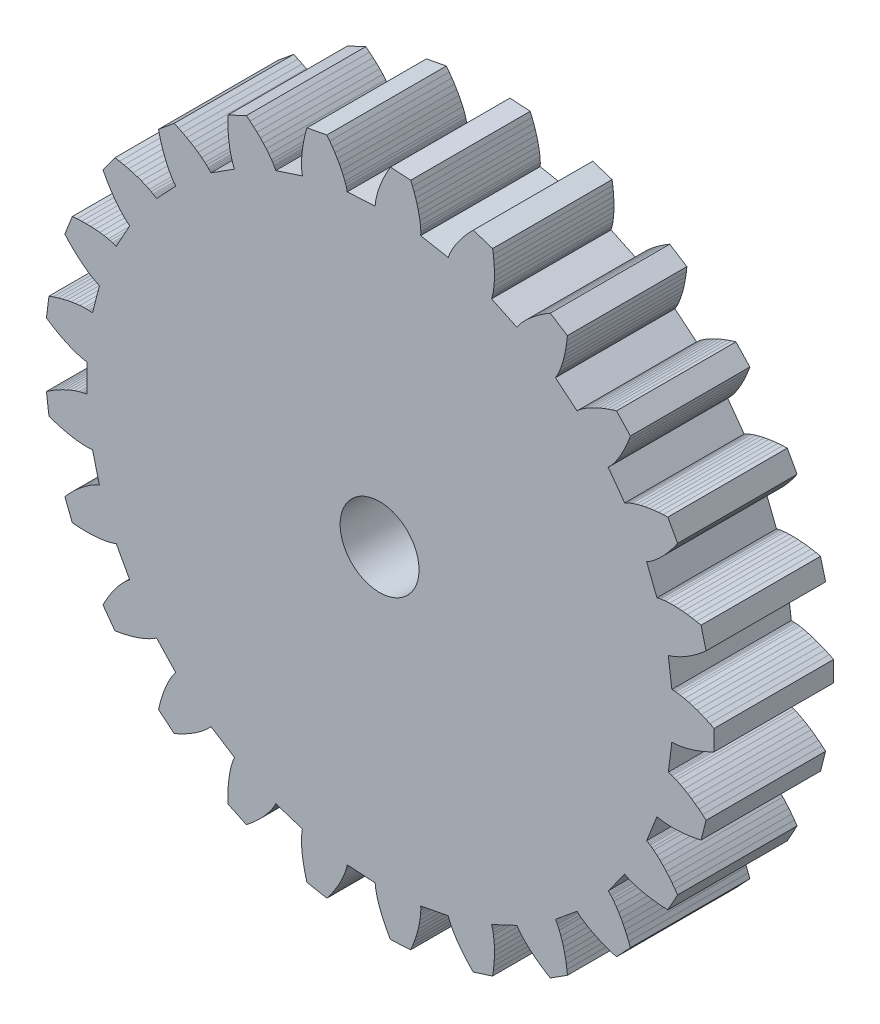
SolidWorks part; units mm, degrees
ref_plane "Front Plane" through (0, 0, 0) normal (0, 0, 1) x (1, 0, 0)
ref_plane "Top Plane" through (0, 0, 0) normal (0, 1, 0) x (1, 0, 0)
ref_plane "Right Plane" through (0, 0, 0) normal (1, 0, 0) x (0, 0, -1)
sketch "Model" plane through (0, 0, 0) normal (0, 0, 1) x (1, 0, 0)
  line L0 (22.5153, 13.4937) -> (22.5501, 13.4944)
  line L1 (22.5501, 13.4944) -> (22.5851, 13.4936)
  line L2 (22.5851, 13.4936) -> (22.6201, 13.4916)
  line L3 (22.6201, 13.4916) -> (22.6552, 13.4888)
  line L4 (22.6552, 13.4888) -> (22.7255, 13.481)
  line L5 (22.7255, 13.481) -> (22.796, 13.4706)
  line L6 (22.796, 13.4706) -> (22.9373, 13.4433)
  line L7 (22.9373, 13.4433) -> (23.079, 13.4085)
  line L8 (23.079, 13.4085) -> (23.221, 13.3669)
  line L9 (23.221, 13.3669) -> (23.363, 13.3191)
  line L10 (23.363, 13.3191) -> (23.5051, 13.2655)
  line L11 (23.5051, 13.2655) -> (23.647, 13.2062)
  line L12 (23.647, 13.2062) -> (23.7888, 13.1416)
  line L13 (23.7888, 13.1416) -> (23.9303, 13.0718)
  line L14 (23.9303, 13.0718) -> (23.9303, 12.3915)
  line L15 (23.9303, 12.3915) -> (23.7888, 12.3217)
  line L16 (23.7888, 12.3217) -> (23.647, 12.257)
  line L17 (23.647, 12.257) -> (23.5051, 12.1978)
  line L18 (23.5051, 12.1978) -> (23.363, 12.1441)
  line L19 (23.363, 12.1441) -> (23.221, 12.0963)
  line L20 (23.221, 12.0963) -> (23.079, 12.0548)
  line L21 (23.079, 12.0548) -> (22.9373, 12.0199)
  line L22 (22.9373, 12.0199) -> (22.796, 11.9927)
  line L23 (22.796, 11.9927) -> (22.7255, 11.9823)
  line L24 (22.7255, 11.9823) -> (22.6552, 11.9745)
  line L25 (22.6552, 11.9745) -> (22.6201, 11.9716)
  line L26 (22.6201, 11.9716) -> (22.5851, 11.9697)
  line L27 (22.5851, 11.9697) -> (22.5501, 11.9688)
  line L28 (22.5501, 11.9688) -> (22.5153, 11.9696)
  line L29 (22.5153, 11.9696) -> (22.3975, 11.0367)
  line L30 (22.3975, 11.0367) -> (22.4314, 11.0287)
  line L31 (22.4314, 11.0287) -> (22.465, 11.0192)
  line L32 (22.465, 11.0192) -> (22.4984, 11.0086)
  line L33 (22.4984, 11.0086) -> (22.5317, 10.9971)
  line L34 (22.5317, 10.9971) -> (22.5978, 10.9721)
  line L35 (22.5978, 10.9721) -> (22.6635, 10.9445)
  line L36 (22.6635, 10.9445) -> (22.7937, 10.8829)
  line L37 (22.7937, 10.8829) -> (22.9223, 10.8139)
  line L38 (22.9223, 10.8139) -> (23.0494, 10.7384)
  line L39 (23.0494, 10.7384) -> (23.1751, 10.6567)
  line L40 (23.1751, 10.6567) -> (23.2994, 10.5694)
  line L41 (23.2994, 10.5694) -> (23.4221, 10.4767)
  line L42 (23.4221, 10.4767) -> (23.5434, 10.3789)
  line L43 (23.5434, 10.3789) -> (23.6631, 10.2761)
  line L44 (23.6631, 10.2761) -> (23.4939, 9.6172)
  line L45 (23.4939, 9.6172) -> (23.3395, 9.5847)
  line L46 (23.3395, 9.5847) -> (23.1861, 9.5574)
  line L47 (23.1861, 9.5574) -> (23.0339, 9.5353)
  line L48 (23.0339, 9.5353) -> (22.8829, 9.5187)
  line L49 (22.8829, 9.5187) -> (22.7334, 9.5077)
  line L50 (22.7334, 9.5077) -> (22.5856, 9.5027)
  line L51 (22.5856, 9.5027) -> (22.4397, 9.5042)
  line L52 (22.4397, 9.5042) -> (22.296, 9.513)
  line L53 (22.296, 9.513) -> (22.2251, 9.5205)
  line L54 (22.2251, 9.5205) -> (22.1551, 9.5304)
  line L55 (22.1551, 9.5304) -> (22.1204, 9.5364)
  line L56 (22.1204, 9.5364) -> (22.086, 9.5432)
  line L57 (22.086, 9.5432) -> (22.0519, 9.551)
  line L58 (22.0519, 9.551) -> (22.0184, 9.5604)
  line L59 (22.0184, 9.5604) -> (21.6723, 8.6861)
  line L60 (21.6723, 8.6861) -> (21.7031, 8.67)
  line L61 (21.7031, 8.67) -> (21.7333, 8.6524)
  line L62 (21.7333, 8.6524) -> (21.7631, 8.6338)
  line L63 (21.7631, 8.6338) -> (21.7925, 8.6145)
  line L64 (21.7925, 8.6145) -> (21.8503, 8.5737)
  line L65 (21.8503, 8.5737) -> (21.9071, 8.5306)
  line L66 (21.9071, 8.5306) -> (22.0178, 8.4387)
  line L67 (22.0178, 8.4387) -> (22.1252, 8.3399)
  line L68 (22.1252, 8.3399) -> (22.2296, 8.2351)
  line L69 (22.2296, 8.2351) -> (22.331, 8.1247)
  line L70 (22.331, 8.1247) -> (22.4297, 8.0093)
  line L71 (22.4297, 8.0093) -> (22.5255, 7.889)
  line L72 (22.5255, 7.889) -> (22.6186, 7.764)
  line L73 (22.6186, 7.764) -> (22.709, 7.6347)
  line L74 (22.709, 7.6347) -> (22.3812, 7.0385)
  line L75 (22.3812, 7.0385) -> (22.2236, 7.0455)
  line L76 (22.2236, 7.0455) -> (22.0683, 7.0572)
  line L77 (22.0683, 7.0572) -> (21.9153, 7.0737)
  line L78 (21.9153, 7.0737) -> (21.765, 7.0951)
  line L79 (21.765, 7.0951) -> (21.6175, 7.1216)
  line L80 (21.6175, 7.1216) -> (21.473, 7.1536)
  line L81 (21.473, 7.1536) -> (21.3321, 7.1913)
  line L82 (21.3321, 7.1913) -> (21.1951, 7.2356)
  line L83 (21.1951, 7.2356) -> (21.1283, 7.2604)
  line L84 (21.1283, 7.2604) -> (21.0629, 7.2874)
  line L85 (21.0629, 7.2874) -> (21.0308, 7.3018)
  line L86 (21.0308, 7.3018) -> (20.9992, 7.317)
  line L87 (20.9992, 7.317) -> (20.9681, 7.3331)
  line L88 (20.9681, 7.3331) -> (20.938, 7.3505)
  line L89 (20.938, 7.3505) -> (20.3853, 6.5898)
  line L90 (20.3853, 6.5898) -> (20.4112, 6.5665)
  line L91 (20.4112, 6.5665) -> (20.4361, 6.5419)
  line L92 (20.4361, 6.5419) -> (20.4602, 6.5165)
  line L93 (20.4602, 6.5165) -> (20.4839, 6.4905)
  line L94 (20.4839, 6.4905) -> (20.5298, 6.4366)
  line L95 (20.5298, 6.4366) -> (20.574, 6.3808)
  line L96 (20.574, 6.3808) -> (20.6584, 6.2642)
  line L97 (20.6584, 6.2642) -> (20.7379, 6.1418)
  line L98 (20.7379, 6.1418) -> (20.8129, 6.0143)
  line L99 (20.8129, 6.0143) -> (20.8838, 5.8822)
  line L100 (20.8838, 5.8822) -> (20.9506, 5.7458)
  line L101 (20.9506, 5.7458) -> (21.0135, 5.6055)
  line L102 (21.0135, 5.6055) -> (21.0726, 5.4613)
  line L103 (21.0726, 5.4613) -> (21.128, 5.3136)
  line L104 (21.128, 5.3136) -> (20.6622, 4.8176)
  line L105 (20.6622, 4.8176) -> (20.5113, 4.8636)
  line L106 (20.5113, 4.8636) -> (20.3638, 4.9136)
  line L107 (20.3638, 4.9136) -> (20.2197, 4.9675)
  line L108 (20.2197, 4.9675) -> (20.0794, 5.0257)
  line L109 (20.0794, 5.0257) -> (19.9432, 5.0881)
  line L110 (19.9432, 5.0881) -> (19.8112, 5.1549)
  line L111 (19.8112, 5.1549) -> (19.6841, 5.2265)
  line L112 (19.6841, 5.2265) -> (19.5624, 5.3035)
  line L113 (19.5624, 5.3035) -> (19.5039, 5.3441)
  line L114 (19.5039, 5.3441) -> (19.4472, 5.3866)
  line L115 (19.4472, 5.3866) -> (19.4197, 5.4085)
  line L116 (19.4197, 5.4085) -> (19.3929, 5.4311)
  line L117 (19.3929, 5.4311) -> (19.3668, 5.4543)
  line L118 (19.3668, 5.4543) -> (19.3419, 5.4787)
  line L119 (19.3419, 5.4787) -> (18.6174, 4.8793)
  line L120 (18.6174, 4.8793) -> (18.6367, 4.8503)
  line L121 (18.6367, 4.8503) -> (18.6547, 4.8204)
  line L122 (18.6547, 4.8204) -> (18.6718, 4.7898)
  line L123 (18.6718, 4.7898) -> (18.6882, 4.7586)
  line L124 (18.6882, 4.7586) -> (18.7193, 4.6951)
  line L125 (18.7193, 4.6951) -> (18.7483, 4.63)
  line L126 (18.7483, 4.63) -> (18.801, 4.496)
  line L127 (18.801, 4.496) -> (18.8476, 4.3577)
  line L128 (18.8476, 4.3577) -> (18.8885, 4.2156)
  line L129 (18.8885, 4.2156) -> (18.9243, 4.07)
  line L130 (18.9243, 4.07) -> (18.9551, 3.9213)
  line L131 (18.9551, 3.9213) -> (18.9811, 3.7697)
  line L132 (18.9811, 3.7697) -> (19.0025, 3.6154)
  line L133 (19.0025, 3.6154) -> (19.0194, 3.4586)
  line L134 (19.0194, 3.4586) -> (18.445, 3.094)
  line L135 (18.445, 3.094) -> (18.3102, 3.1761)
  line L136 (18.3102, 3.1761) -> (18.1797, 3.2611)
  line L137 (18.1797, 3.2611) -> (18.0536, 3.3493)
  line L138 (18.0536, 3.3493) -> (17.9322, 3.4404)
  line L139 (17.9322, 3.4404) -> (17.8157, 3.5348)
  line L140 (17.8157, 3.5348) -> (17.7045, 3.6323)
  line L141 (17.7045, 3.6323) -> (17.5992, 3.7333)
  line L142 (17.5992, 3.7333) -> (17.5004, 3.8381)
  line L143 (17.5004, 3.8381) -> (17.4539, 3.892)
  line L144 (17.4539, 3.892) -> (17.4096, 3.9472)
  line L145 (17.4096, 3.9472) -> (17.3884, 3.9753)
  line L146 (17.3884, 3.9753) -> (17.368, 4.0038)
  line L147 (17.368, 4.0038) -> (17.3486, 4.0329)
  line L148 (17.3486, 4.0329) -> (17.3305, 4.0626)
  line L149 (17.3305, 4.0626) -> (16.4797, 3.6623)
  line L150 (16.4797, 3.6623) -> (16.4912, 3.6294)
  line L151 (16.4912, 3.6294) -> (16.5012, 3.5959)
  line L152 (16.5012, 3.5959) -> (16.5101, 3.562)
  line L153 (16.5101, 3.562) -> (16.5183, 3.5278)
  line L154 (16.5183, 3.5278) -> (16.5326, 3.4585)
  line L155 (16.5326, 3.4585) -> (16.5445, 3.3882)
  line L156 (16.5445, 3.3882) -> (16.5622, 3.2454)
  line L157 (16.5622, 3.2454) -> (16.5729, 3.0998)
  line L158 (16.5729, 3.0998) -> (16.5772, 2.952)
  line L159 (16.5772, 2.952) -> (16.5756, 2.8021)
  line L160 (16.5756, 2.8021) -> (16.5685, 2.6504)
  line L161 (16.5685, 2.6504) -> (16.556, 2.4971)
  line L162 (16.556, 2.4971) -> (16.5384, 2.3423)
  line L163 (16.5384, 2.3423) -> (16.5157, 2.1862)
  line L164 (16.5157, 2.1862) -> (15.8687, 1.9759)
  line L165 (15.8687, 1.9759) -> (15.7586, 2.0889)
  line L166 (15.7586, 2.0889) -> (15.6533, 2.2038)
  line L167 (15.6533, 2.2038) -> (15.5531, 2.3205)
  line L168 (15.5531, 2.3205) -> (15.4582, 2.439)
  line L169 (15.4582, 2.439) -> (15.3688, 2.5593)
  line L170 (15.3688, 2.5593) -> (15.2854, 2.6815)
  line L171 (15.2854, 2.6815) -> (15.2085, 2.8055)
  line L172 (15.2085, 2.8055) -> (15.1389, 2.9315)
  line L173 (15.1389, 2.9315) -> (15.1072, 2.9954)
  line L174 (15.1072, 2.9954) -> (15.078, 3.0598)
  line L175 (15.078, 3.0598) -> (15.0645, 3.0923)
  line L176 (15.0645, 3.0923) -> (15.0519, 3.125)
  line L177 (15.0519, 3.125) -> (15.0402, 3.158)
  line L178 (15.0402, 3.158) -> (15.0302, 3.1913)
  line L179 (15.0302, 3.1913) -> (14.1065, 3.0151)
  line L180 (14.1065, 3.0151) -> (14.1095, 2.9804)
  line L181 (14.1095, 2.9804) -> (14.1108, 2.9455)
  line L182 (14.1108, 2.9455) -> (14.111, 2.9104)
  line L183 (14.111, 2.9104) -> (14.1104, 2.8752)
  line L184 (14.1104, 2.8752) -> (14.107, 2.8046)
  line L185 (14.107, 2.8046) -> (14.1011, 2.7336)
  line L186 (14.1011, 2.7336) -> (14.0827, 2.5908)
  line L187 (14.0827, 2.5908) -> (14.0569, 2.4471)
  line L188 (14.0569, 2.4471) -> (14.0243, 2.3029)
  line L189 (14.0243, 2.3029) -> (13.9855, 2.1581)
  line L190 (13.9855, 2.1581) -> (13.9409, 2.0129)
  line L191 (13.9409, 2.0129) -> (13.8907, 1.8675)
  line L192 (13.8907, 1.8675) -> (13.8351, 1.722)
  line L193 (13.8351, 1.722) -> (13.7743, 1.5764)
  line L194 (13.7743, 1.5764) -> (13.0953, 1.5337)
  line L195 (13.0953, 1.5337) -> (13.0168, 1.6705)
  line L196 (13.0168, 1.6705) -> (12.9434, 1.808)
  line L197 (12.9434, 1.808) -> (12.8753, 1.9459)
  line L198 (12.8753, 1.9459) -> (12.8128, 2.0843)
  line L199 (12.8128, 2.0843) -> (12.7562, 2.2231)
  line L200 (12.7562, 2.2231) -> (12.7058, 2.3621)
  line L201 (12.7058, 2.3621) -> (12.6622, 2.5014)
  line L202 (12.6622, 2.5014) -> (12.6261, 2.6408)
  line L203 (12.6261, 2.6408) -> (12.6113, 2.7105)
  line L204 (12.6113, 2.7105) -> (12.599, 2.7801)
  line L205 (12.599, 2.7801) -> (12.594, 2.815)
  line L206 (12.594, 2.815) -> (12.5899, 2.8498)
  line L207 (12.5899, 2.8498) -> (12.5868, 2.8846)
  line L208 (12.5868, 2.8846) -> (12.5854, 2.9194)
  line L209 (12.5854, 2.9194) -> (11.6469, 2.9784)
  line L210 (11.6469, 2.9784) -> (11.6411, 2.9441)
  line L211 (11.6411, 2.9441) -> (11.6337, 2.91)
  line L212 (11.6337, 2.91) -> (11.6253, 2.8759)
  line L213 (11.6253, 2.8759) -> (11.6159, 2.842)
  line L214 (11.6159, 2.842) -> (11.595, 2.7744)
  line L215 (11.595, 2.7744) -> (11.5716, 2.7071)
  line L216 (11.5716, 2.7071) -> (11.5184, 2.5733)
  line L217 (11.5184, 2.5733) -> (11.4576, 2.4407)
  line L218 (11.4576, 2.4407) -> (11.3902, 2.309)
  line L219 (11.3902, 2.309) -> (11.3166, 2.1784)
  line L220 (11.3166, 2.1784) -> (11.2372, 2.049)
  line L221 (11.2372, 2.049) -> (11.1525, 1.9206)
  line L222 (11.1525, 1.9206) -> (11.0624, 1.7935)
  line L223 (11.0624, 1.7935) -> (10.9673, 1.6676)
  line L224 (10.9673, 1.6676) -> (10.2991, 1.7951)
  line L225 (10.2991, 1.7951) -> (10.257, 1.9471)
  line L226 (10.257, 1.9471) -> (10.2201, 2.0985)
  line L227 (10.2201, 2.0985) -> (10.1885, 2.249)
  line L228 (10.1885, 2.249) -> (10.1624, 2.3986)
  line L229 (10.1624, 2.3986) -> (10.1421, 2.5471)
  line L230 (10.1421, 2.5471) -> (10.1278, 2.6943)
  line L231 (10.1278, 2.6943) -> (10.1202, 2.8401)
  line L232 (10.1202, 2.8401) -> (10.1199, 2.984)
  line L233 (10.1199, 2.984) -> (10.1229, 3.0552)
  line L234 (10.1229, 3.0552) -> (10.1284, 3.1258)
  line L235 (10.1284, 3.1258) -> (10.1322, 3.1607)
  line L236 (10.1322, 3.1607) -> (10.1368, 3.1955)
  line L237 (10.1368, 3.1955) -> (10.1425, 3.23)
  line L238 (10.1425, 3.23) -> (10.1498, 3.264)
  line L239 (10.1498, 3.264) -> (9.2555, 3.5546)
  line L240 (9.2555, 3.5546) -> (9.2413, 3.5228)
  line L241 (9.2413, 3.5228) -> (9.2257, 3.4916)
  line L242 (9.2257, 3.4916) -> (9.209, 3.4607)
  line L243 (9.209, 3.4607) -> (9.1915, 3.4302)
  line L244 (9.1915, 3.4302) -> (9.1545, 3.3699)
  line L245 (9.1545, 3.3699) -> (9.1151, 3.3105)
  line L246 (9.1151, 3.3105) -> (9.0302, 3.1942)
  line L247 (9.0302, 3.1942) -> (8.9384, 3.0808)
  line L248 (8.9384, 3.0808) -> (8.8403, 2.9701)
  line L249 (8.8403, 2.9701) -> (8.7366, 2.8619)
  line L250 (8.7366, 2.8619) -> (8.6275, 2.7562)
  line L251 (8.6275, 2.7562) -> (8.5135, 2.653)
  line L252 (8.5135, 2.653) -> (8.3947, 2.5522)
  line L253 (8.3947, 2.5522) -> (8.2713, 2.4539)
  line L254 (8.2713, 2.4539) -> (7.6557, 2.7436)
  line L255 (7.6557, 2.7436) -> (7.6528, 2.9013)
  line L256 (7.6528, 2.9013) -> (7.6547, 3.0571)
  line L257 (7.6547, 3.0571) -> (7.6615, 3.2108)
  line L258 (7.6615, 3.2108) -> (7.6734, 3.3622)
  line L259 (7.6734, 3.3622) -> (7.6906, 3.5111)
  line L260 (7.6906, 3.5111) -> (7.7135, 3.6572)
  line L261 (7.7135, 3.6572) -> (7.7423, 3.8003)
  line L262 (7.7423, 3.8003) -> (7.7778, 3.9398)
  line L263 (7.7778, 3.9398) -> (7.7984, 4.008)
  line L264 (7.7984, 4.008) -> (7.8213, 4.0749)
  line L265 (7.8213, 4.0749) -> (7.8337, 4.1079)
  line L266 (7.8337, 4.1079) -> (7.8468, 4.1404)
  line L267 (7.8468, 4.1404) -> (7.8609, 4.1724)
  line L268 (7.8609, 4.1724) -> (7.8764, 4.2036)
  line L269 (7.8764, 4.2036) -> (7.0825, 4.7074)
  line L270 (7.0825, 4.7074) -> (7.0608, 4.6801)
  line L271 (7.0608, 4.6801) -> (7.0379, 4.6537)
  line L272 (7.0379, 4.6537) -> (7.0141, 4.628)
  line L273 (7.0141, 4.628) -> (6.9896, 4.6028)
  line L274 (6.9896, 4.6028) -> (6.9387, 4.5536)
  line L275 (6.9387, 4.5536) -> (6.8858, 4.5059)
  line L276 (6.8858, 4.5059) -> (6.7746, 4.4144)
  line L277 (6.7746, 4.4144) -> (6.6575, 4.3274)
  line L278 (6.6575, 4.3274) -> (6.535, 4.2445)
  line L279 (6.535, 4.2445) -> (6.4076, 4.1655)
  line L280 (6.4076, 4.1655) -> (6.2757, 4.0903)
  line L281 (6.2757, 4.0903) -> (6.1395, 4.0186)
  line L282 (6.1395, 4.0186) -> (5.9994, 3.9506)
  line L283 (5.9994, 3.9506) -> (5.8554, 3.8861)
  line L284 (5.8554, 3.8861) -> (5.3312, 4.3197)
  line L285 (5.3312, 4.3197) -> (5.3676, 4.4732)
  line L286 (5.3676, 4.4732) -> (5.4082, 4.6237)
  line L287 (5.4082, 4.6237) -> (5.453, 4.7708)
  line L288 (5.453, 4.7708) -> (5.5022, 4.9145)
  line L289 (5.5022, 4.9145) -> (5.556, 5.0544)
  line L290 (5.556, 5.0544) -> (5.6144, 5.1903)
  line L291 (5.6144, 5.1903) -> (5.6779, 5.3217)
  line L292 (5.6779, 5.3217) -> (5.747, 5.4479)
  line L293 (5.747, 5.4479) -> (5.7839, 5.5089)
  line L294 (5.7839, 5.5089) -> (5.8227, 5.5681)
  line L295 (5.8227, 5.5681) -> (5.8429, 5.5969)
  line L296 (5.8429, 5.5969) -> (5.8637, 5.6251)
  line L297 (5.8637, 5.6251) -> (5.8853, 5.6526)
  line L298 (5.8853, 5.6526) -> (5.9081, 5.6789)
  line L299 (5.9081, 5.6789) -> (5.2644, 6.3644)
  line L300 (5.2644, 6.3644) -> (5.2367, 6.3433)
  line L301 (5.2367, 6.3433) -> (5.2079, 6.3235)
  line L302 (5.2079, 6.3235) -> (5.1784, 6.3045)
  line L303 (5.1784, 6.3045) -> (5.1484, 6.2862)
  line L304 (5.1484, 6.2862) -> (5.0869, 6.2512)
  line L305 (5.0869, 6.2512) -> (5.0238, 6.2181)
  line L306 (5.0238, 6.2181) -> (4.8934, 6.1571)
  line L307 (4.8934, 6.1571) -> (4.7583, 6.102)
  line L308 (4.7583, 6.102) -> (4.619, 6.0522)
  line L309 (4.619, 6.0522) -> (4.476, 6.0074)
  line L310 (4.476, 6.0074) -> (4.3295, 5.9673)
  line L311 (4.3295, 5.9673) -> (4.1798, 5.9318)
  line L312 (4.1798, 5.9318) -> (4.0272, 5.9007)
  line L313 (4.0272, 5.9007) -> (3.8717, 5.874)
  line L314 (3.8717, 5.874) -> (3.4718, 6.4244)
  line L315 (3.4718, 6.4244) -> (3.5452, 6.5641)
  line L316 (3.5452, 6.5641) -> (3.6219, 6.6996)
  line L317 (3.6219, 6.6996) -> (3.7019, 6.831)
  line L318 (3.7019, 6.831) -> (3.7853, 6.9579)
  line L319 (3.7853, 6.9579) -> (3.8721, 7.0801)
  line L320 (3.8721, 7.0801) -> (3.9625, 7.1972)
  line L321 (3.9625, 7.1972) -> (4.0567, 7.3086)
  line L322 (4.0567, 7.3086) -> (4.1551, 7.4138)
  line L323 (4.1551, 7.4138) -> (4.206, 7.4636)
  line L324 (4.206, 7.4636) -> (4.2583, 7.5113)
  line L325 (4.2583, 7.5113) -> (4.285, 7.5342)
  line L326 (4.285, 7.5342) -> (4.3122, 7.5563)
  line L327 (4.3122, 7.5563) -> (4.3399, 7.5776)
  line L328 (4.3399, 7.5776) -> (4.3685, 7.5975)
  line L329 (4.3685, 7.5975) -> (3.9155, 8.4215)
  line L330 (3.9155, 8.4215) -> (3.8834, 8.4079)
  line L331 (3.8834, 8.4079) -> (3.8506, 8.3959)
  line L332 (3.8506, 8.3959) -> (3.8174, 8.3848)
  line L333 (3.8174, 8.3848) -> (3.7837, 8.3745)
  line L334 (3.7837, 8.3745) -> (3.7154, 8.3559)
  line L335 (3.7154, 8.3559) -> (3.6461, 8.3396)
  line L336 (3.6461, 8.3396) -> (3.5046, 8.3129)
  line L337 (3.5046, 8.3129) -> (3.36, 8.2932)
  line L338 (3.36, 8.2932) -> (3.2127, 8.2796)
  line L339 (3.2127, 8.2796) -> (3.0631, 8.2717)
  line L340 (3.0631, 8.2717) -> (2.9112, 8.2693)
  line L341 (2.9112, 8.2693) -> (2.7574, 8.2721)
  line L342 (2.7574, 8.2721) -> (2.6018, 8.28)
  line L343 (2.6018, 8.28) -> (2.4446, 8.2928)
  line L344 (2.4446, 8.2928) -> (2.1941, 8.9254)
  line L345 (2.1941, 8.9254) -> (2.3, 9.0424)
  line L346 (2.3, 9.0424) -> (2.408, 9.1547)
  line L347 (2.408, 9.1547) -> (2.5182, 9.262)
  line L348 (2.5182, 9.262) -> (2.6305, 9.3642)
  line L349 (2.6305, 9.3642) -> (2.745, 9.4609)
  line L350 (2.745, 9.4609) -> (2.8617, 9.5518)
  line L351 (2.8617, 9.5518) -> (2.9806, 9.6364)
  line L352 (2.9806, 9.6364) -> (3.102, 9.7138)
  line L353 (3.102, 9.7138) -> (3.1637, 9.7494)
  line L354 (3.1637, 9.7494) -> (3.2262, 9.7825)
  line L355 (3.2262, 9.7825) -> (3.2578, 9.7981)
  line L356 (3.2578, 9.7981) -> (3.2897, 9.8128)
  line L357 (3.2897, 9.8128) -> (3.3218, 9.8265)
  line L358 (3.3218, 9.8265) -> (3.3544, 9.8386)
  line L359 (3.3544, 9.8386) -> (3.1206, 10.7493)
  line L360 (3.1206, 10.7493) -> (3.0862, 10.7442)
  line L361 (3.0862, 10.7442) -> (3.0514, 10.7407)
  line L362 (3.0514, 10.7407) -> (3.0164, 10.7383)
  line L363 (3.0164, 10.7383) -> (2.9813, 10.7367)
  line L364 (2.9813, 10.7367) -> (2.9105, 10.7356)
  line L365 (2.9105, 10.7356) -> (2.8393, 10.7371)
  line L366 (2.8393, 10.7371) -> (2.6956, 10.7464)
  line L367 (2.6956, 10.7464) -> (2.5506, 10.7632)
  line L368 (2.5506, 10.7632) -> (2.4046, 10.7867)
  line L369 (2.4046, 10.7867) -> (2.2577, 10.8163)
  line L370 (2.2577, 10.8163) -> (2.11, 10.8517)
  line L371 (2.11, 10.8517) -> (1.9618, 10.8927)
  line L372 (1.9618, 10.8927) -> (1.813, 10.9391)
  line L373 (1.813, 10.9391) -> (1.6639, 10.9906)
  line L374 (1.6639, 10.9906) -> (1.5786, 11.6655)
  line L375 (1.5786, 11.6655) -> (1.7103, 11.7525)
  line L376 (1.7103, 11.7525) -> (1.8428, 11.8344)
  line L377 (1.8428, 11.8344) -> (1.9762, 11.911)
  line L378 (1.9762, 11.911) -> (2.1104, 11.982)
  line L379 (2.1104, 11.982) -> (2.2454, 12.0472)
  line L380 (2.2454, 12.0472) -> (2.381, 12.1063)
  line L381 (2.381, 12.1063) -> (2.5172, 12.1586)
  line L382 (2.5172, 12.1586) -> (2.654, 12.2034)
  line L383 (2.654, 12.2034) -> (2.7227, 12.2225)
  line L384 (2.7227, 12.2225) -> (2.7915, 12.2391)
  line L385 (2.7915, 12.2391) -> (2.8259, 12.2463)
  line L386 (2.8259, 12.2463) -> (2.8604, 12.2526)
  line L387 (2.8604, 12.2526) -> (2.8949, 12.2578)
  line L388 (2.8949, 12.2578) -> (2.9296, 12.2615)
  line L389 (2.9296, 12.2615) -> (2.9296, 13.2018)
  line L390 (2.9296, 13.2018) -> (2.8949, 13.2054)
  line L391 (2.8949, 13.2054) -> (2.8604, 13.2107)
  line L392 (2.8604, 13.2107) -> (2.8259, 13.217)
  line L393 (2.8259, 13.217) -> (2.7915, 13.2242)
  line L394 (2.7915, 13.2242) -> (2.7227, 13.2408)
  line L395 (2.7227, 13.2408) -> (2.654, 13.2599)
  line L396 (2.654, 13.2599) -> (2.5172, 13.3047)
  line L397 (2.5172, 13.3047) -> (2.381, 13.357)
  line L398 (2.381, 13.357) -> (2.2454, 13.416)
  line L399 (2.2454, 13.416) -> (2.1104, 13.4812)
  line L400 (2.1104, 13.4812) -> (1.9762, 13.5523)
  line L401 (1.9762, 13.5523) -> (1.8428, 13.6289)
  line L402 (1.8428, 13.6289) -> (1.7103, 13.7107)
  line L403 (1.7103, 13.7107) -> (1.5786, 13.7977)
  line L404 (1.5786, 13.7977) -> (1.6639, 14.4727)
  line L405 (1.6639, 14.4727) -> (1.813, 14.5242)
  line L406 (1.813, 14.5242) -> (1.9618, 14.5705)
  line L407 (1.9618, 14.5705) -> (2.11, 14.6115)
  line L408 (2.11, 14.6115) -> (2.2577, 14.647)
  line L409 (2.2577, 14.647) -> (2.4046, 14.6766)
  line L410 (2.4046, 14.6766) -> (2.5506, 14.7)
  line L411 (2.5506, 14.7) -> (2.6956, 14.7168)
  line L412 (2.6956, 14.7168) -> (2.8393, 14.7261)
  line L413 (2.8393, 14.7261) -> (2.9105, 14.7276)
  line L414 (2.9105, 14.7276) -> (2.9813, 14.7266)
  line L415 (2.9813, 14.7266) -> (3.0164, 14.725)
  line L416 (3.0164, 14.725) -> (3.0514, 14.7225)
  line L417 (3.0514, 14.7225) -> (3.0862, 14.719)
  line L418 (3.0862, 14.719) -> (3.1206, 14.7139)
  line L419 (3.1206, 14.7139) -> (3.3544, 15.6247)
  line L420 (3.3544, 15.6247) -> (3.3218, 15.6368)
  line L421 (3.3218, 15.6368) -> (3.2897, 15.6505)
  line L422 (3.2897, 15.6505) -> (3.2578, 15.6652)
  line L423 (3.2578, 15.6652) -> (3.2262, 15.6807)
  line L424 (3.2262, 15.6807) -> (3.1637, 15.7139)
  line L425 (3.1637, 15.7139) -> (3.102, 15.7495)
  line L426 (3.102, 15.7495) -> (2.9806, 15.8269)
  line L427 (2.9806, 15.8269) -> (2.8617, 15.9114)
  line L428 (2.8617, 15.9114) -> (2.745, 16.0023)
  line L429 (2.745, 16.0023) -> (2.6305, 16.0991)
  line L430 (2.6305, 16.0991) -> (2.5182, 16.2013)
  line L431 (2.5182, 16.2013) -> (2.408, 16.3086)
  line L432 (2.408, 16.3086) -> (2.3, 16.4209)
  line L433 (2.3, 16.4209) -> (2.1941, 16.5379)
  line L434 (2.1941, 16.5379) -> (2.4446, 17.1704)
  line L435 (2.4446, 17.1704) -> (2.6018, 17.1832)
  line L436 (2.6018, 17.1832) -> (2.7574, 17.1911)
  line L437 (2.7574, 17.1911) -> (2.9112, 17.1939)
  line L438 (2.9112, 17.1939) -> (3.0631, 17.1915)
  line L439 (3.0631, 17.1915) -> (3.2127, 17.1837)
  line L440 (3.2127, 17.1837) -> (3.36, 17.1701)
  line L441 (3.36, 17.1701) -> (3.5046, 17.1503)
  line L442 (3.5046, 17.1503) -> (3.6461, 17.1236)
  line L443 (3.6461, 17.1236) -> (3.7154, 17.1073)
  line L444 (3.7154, 17.1073) -> (3.7837, 17.0887)
  line L445 (3.7837, 17.0887) -> (3.8174, 17.0784)
  line L446 (3.8174, 17.0784) -> (3.8506, 17.0674)
  line L447 (3.8506, 17.0674) -> (3.8834, 17.0553)
  line L448 (3.8834, 17.0553) -> (3.9155, 17.0418)
  line L449 (3.9155, 17.0418) -> (4.3685, 17.8658)
  line L450 (4.3685, 17.8658) -> (4.3399, 17.8857)
  line L451 (4.3399, 17.8857) -> (4.3122, 17.9069)
  line L452 (4.3122, 17.9069) -> (4.285, 17.9291)
  line L453 (4.285, 17.9291) -> (4.2583, 17.952)
  line L454 (4.2583, 17.952) -> (4.206, 17.9996)
  line L455 (4.206, 17.9996) -> (4.1551, 18.0495)
  line L456 (4.1551, 18.0495) -> (4.0567, 18.1546)
  line L457 (4.0567, 18.1546) -> (3.9625, 18.2661)
  line L458 (3.9625, 18.2661) -> (3.8721, 18.3831)
  line L459 (3.8721, 18.3831) -> (3.7853, 18.5053)
  line L460 (3.7853, 18.5053) -> (3.7019, 18.6322)
  line L461 (3.7019, 18.6322) -> (3.6219, 18.7636)
  line L462 (3.6219, 18.7636) -> (3.5452, 18.8992)
  line L463 (3.5452, 18.8992) -> (3.4718, 19.0388)
  line L464 (3.4718, 19.0388) -> (3.8717, 19.5892)
  line L465 (3.8717, 19.5892) -> (4.0272, 19.5626)
  line L466 (4.0272, 19.5626) -> (4.1798, 19.5315)
  line L467 (4.1798, 19.5315) -> (4.3295, 19.496)
  line L468 (4.3295, 19.496) -> (4.476, 19.4559)
  line L469 (4.476, 19.4559) -> (4.619, 19.4111)
  line L470 (4.619, 19.4111) -> (4.7583, 19.3613)
  line L471 (4.7583, 19.3613) -> (4.8934, 19.3062)
  line L472 (4.8934, 19.3062) -> (5.0238, 19.2451)
  line L473 (5.0238, 19.2451) -> (5.0869, 19.2121)
  line L474 (5.0869, 19.2121) -> (5.1484, 19.1771)
  line L475 (5.1484, 19.1771) -> (5.1784, 19.1588)
  line L476 (5.1784, 19.1588) -> (5.2079, 19.1398)
  line L477 (5.2079, 19.1398) -> (5.2367, 19.1199)
  line L478 (5.2367, 19.1199) -> (5.2644, 19.0989)
  line L479 (5.2644, 19.0989) -> (5.9081, 19.7843)
  line L480 (5.9081, 19.7843) -> (5.8853, 19.8107)
  line L481 (5.8853, 19.8107) -> (5.8637, 19.8381)
  line L482 (5.8637, 19.8381) -> (5.8429, 19.8664)
  line L483 (5.8429, 19.8664) -> (5.8227, 19.8952)
  line L484 (5.8227, 19.8952) -> (5.7839, 19.9544)
  line L485 (5.7839, 19.9544) -> (5.747, 20.0153)
  line L486 (5.747, 20.0153) -> (5.6779, 20.1416)
  line L487 (5.6779, 20.1416) -> (5.6144, 20.273)
  line L488 (5.6144, 20.273) -> (5.556, 20.4089)
  line L489 (5.556, 20.4089) -> (5.5022, 20.5488)
  line L490 (5.5022, 20.5488) -> (5.453, 20.6925)
  line L491 (5.453, 20.6925) -> (5.4082, 20.8396)
  line L492 (5.4082, 20.8396) -> (5.3676, 20.99)
  line L493 (5.3676, 20.99) -> (5.3312, 21.1435)
  line L494 (5.3312, 21.1435) -> (5.8554, 21.5772)
  line L495 (5.8554, 21.5772) -> (5.9994, 21.5127)
  line L496 (5.9994, 21.5127) -> (6.1395, 21.4446)
  line L497 (6.1395, 21.4446) -> (6.2757, 21.373)
  line L498 (6.2757, 21.373) -> (6.4076, 21.2977)
  line L499 (6.4076, 21.2977) -> (6.535, 21.2188)
  line L500 (6.535, 21.2188) -> (6.6575, 21.1359)
  line L501 (6.6575, 21.1359) -> (6.7746, 21.0489)
  line L502 (6.7746, 21.0489) -> (6.8858, 20.9574)
  line L503 (6.8858, 20.9574) -> (6.9387, 20.9097)
  line L504 (6.9387, 20.9097) -> (6.9896, 20.8605)
  line L505 (6.9896, 20.8605) -> (7.0141, 20.8352)
  line L506 (7.0141, 20.8352) -> (7.0379, 20.8095)
  line L507 (7.0379, 20.8095) -> (7.0608, 20.7831)
  line L508 (7.0608, 20.7831) -> (7.0825, 20.7559)
  line L509 (7.0825, 20.7559) -> (7.8764, 21.2597)
  line L510 (7.8764, 21.2597) -> (7.8609, 21.2909)
  line L511 (7.8609, 21.2909) -> (7.8468, 21.3229)
  line L512 (7.8468, 21.3229) -> (7.8337, 21.3554)
  line L513 (7.8337, 21.3554) -> (7.8213, 21.3883)
  line L514 (7.8213, 21.3883) -> (7.7984, 21.4553)
  line L515 (7.7984, 21.4553) -> (7.7778, 21.5235)
  line L516 (7.7778, 21.5235) -> (7.7423, 21.663)
  line L517 (7.7423, 21.663) -> (7.7135, 21.806)
  line L518 (7.7135, 21.806) -> (7.6906, 21.9522)
  line L519 (7.6906, 21.9522) -> (7.6734, 22.1011)
  line L520 (7.6734, 22.1011) -> (7.6615, 22.2525)
  line L521 (7.6615, 22.2525) -> (7.6547, 22.4061)
  line L522 (7.6547, 22.4061) -> (7.6528, 22.5619)
  line L523 (7.6528, 22.5619) -> (7.6557, 22.7196)
  line L524 (7.6557, 22.7196) -> (8.2713, 23.0093)
  line L525 (8.2713, 23.0093) -> (8.3947, 22.911)
  line L526 (8.3947, 22.911) -> (8.5135, 22.8103)
  line L527 (8.5135, 22.8103) -> (8.6275, 22.707)
  line L528 (8.6275, 22.707) -> (8.7366, 22.6013)
  line L529 (8.7366, 22.6013) -> (8.8403, 22.4932)
  line L530 (8.8403, 22.4932) -> (8.9384, 22.3824)
  line L531 (8.9384, 22.3824) -> (9.0302, 22.269)
  line L532 (9.0302, 22.269) -> (9.1151, 22.1527)
  line L533 (9.1151, 22.1527) -> (9.1545, 22.0934)
  line L534 (9.1545, 22.0934) -> (9.1915, 22.0331)
  line L535 (9.1915, 22.0331) -> (9.209, 22.0026)
  line L536 (9.209, 22.0026) -> (9.2257, 21.9717)
  line L537 (9.2257, 21.9717) -> (9.2413, 21.9405)
  line L538 (9.2413, 21.9405) -> (9.2555, 21.9086)
  line L539 (9.2555, 21.9086) -> (10.1498, 22.1992)
  line L540 (10.1498, 22.1992) -> (10.1425, 22.2333)
  line L541 (10.1425, 22.2333) -> (10.1368, 22.2677)
  line L542 (10.1368, 22.2677) -> (10.1322, 22.3025)
  line L543 (10.1322, 22.3025) -> (10.1284, 22.3375)
  line L544 (10.1284, 22.3375) -> (10.1229, 22.408)
  line L545 (10.1229, 22.408) -> (10.1199, 22.4792)
  line L546 (10.1199, 22.4792) -> (10.1202, 22.6232)
  line L547 (10.1202, 22.6232) -> (10.1278, 22.7689)
  line L548 (10.1278, 22.7689) -> (10.1421, 22.9161)
  line L549 (10.1421, 22.9161) -> (10.1624, 23.0646)
  line L550 (10.1624, 23.0646) -> (10.1885, 23.2142)
  line L551 (10.1885, 23.2142) -> (10.2201, 23.3648)
  line L552 (10.2201, 23.3648) -> (10.257, 23.5161)
  line L553 (10.257, 23.5161) -> (10.2991, 23.6682)
  line L554 (10.2991, 23.6682) -> (10.9673, 23.7957)
  line L555 (10.9673, 23.7957) -> (11.0624, 23.6698)
  line L556 (11.0624, 23.6698) -> (11.1525, 23.5426)
  line L557 (11.1525, 23.5426) -> (11.2372, 23.4143)
  line L558 (11.2372, 23.4143) -> (11.3166, 23.2848)
  line L559 (11.3166, 23.2848) -> (11.3902, 23.1542)
  line L560 (11.3902, 23.1542) -> (11.4576, 23.0226)
  line L561 (11.4576, 23.0226) -> (11.5184, 22.8899)
  line L562 (11.5184, 22.8899) -> (11.5716, 22.7562)
  line L563 (11.5716, 22.7562) -> (11.595, 22.6889)
  line L564 (11.595, 22.6889) -> (11.6159, 22.6213)
  line L565 (11.6159, 22.6213) -> (11.6253, 22.5873)
  line L566 (11.6253, 22.5873) -> (11.6337, 22.5533)
  line L567 (11.6337, 22.5533) -> (11.6411, 22.5191)
  line L568 (11.6411, 22.5191) -> (11.6469, 22.4848)
  line L569 (11.6469, 22.4848) -> (12.5854, 22.5439)
  line L570 (12.5854, 22.5439) -> (12.5868, 22.5786)
  line L571 (12.5868, 22.5786) -> (12.5899, 22.6135)
  line L572 (12.5899, 22.6135) -> (12.594, 22.6483)
  line L573 (12.594, 22.6483) -> (12.599, 22.6831)
  line L574 (12.599, 22.6831) -> (12.6113, 22.7528)
  line L575 (12.6113, 22.7528) -> (12.6261, 22.8225)
  line L576 (12.6261, 22.8225) -> (12.6622, 22.9619)
  line L577 (12.6622, 22.9619) -> (12.7058, 23.1011)
  line L578 (12.7058, 23.1011) -> (12.7562, 23.2402)
  line L579 (12.7562, 23.2402) -> (12.8128, 23.3789)
  line L580 (12.8128, 23.3789) -> (12.8753, 23.5174)
  line L581 (12.8753, 23.5174) -> (12.9434, 23.6553)
  line L582 (12.9434, 23.6553) -> (13.0168, 23.7927)
  line L583 (13.0168, 23.7927) -> (13.0953, 23.9296)
  line L584 (13.0953, 23.9296) -> (13.7743, 23.8868)
  line L585 (13.7743, 23.8868) -> (13.8351, 23.7412)
  line L586 (13.8351, 23.7412) -> (13.8907, 23.5957)
  line L587 (13.8907, 23.5957) -> (13.9409, 23.4503)
  line L588 (13.9409, 23.4503) -> (13.9855, 23.3052)
  line L589 (13.9855, 23.3052) -> (14.0243, 23.1604)
  line L590 (14.0243, 23.1604) -> (14.0569, 23.0161)
  line L591 (14.0569, 23.0161) -> (14.0827, 22.8725)
  line L592 (14.0827, 22.8725) -> (14.1011, 22.7297)
  line L593 (14.1011, 22.7297) -> (14.107, 22.6587)
  line L594 (14.107, 22.6587) -> (14.1104, 22.588)
  line L595 (14.1104, 22.588) -> (14.111, 22.5528)
  line L596 (14.111, 22.5528) -> (14.1108, 22.5178)
  line L597 (14.1108, 22.5178) -> (14.1095, 22.4828)
  line L598 (14.1095, 22.4828) -> (14.1065, 22.4482)
  line L599 (14.1065, 22.4482) -> (15.0302, 22.272)
  line L600 (15.0302, 22.272) -> (15.0402, 22.3053)
  line L601 (15.0402, 22.3053) -> (15.0519, 22.3382)
  line L602 (15.0519, 22.3382) -> (15.0645, 22.3709)
  line L603 (15.0645, 22.3709) -> (15.078, 22.4034)
  line L604 (15.078, 22.4034) -> (15.1072, 22.4679)
  line L605 (15.1072, 22.4679) -> (15.1389, 22.5317)
  line L606 (15.1389, 22.5317) -> (15.2085, 22.6577)
  line L607 (15.2085, 22.6577) -> (15.2854, 22.7818)
  line L608 (15.2854, 22.7818) -> (15.3688, 22.9039)
  line L609 (15.3688, 22.9039) -> (15.4582, 23.0242)
  line L610 (15.4582, 23.0242) -> (15.5531, 23.1428)
  line L611 (15.5531, 23.1428) -> (15.6533, 23.2595)
  line L612 (15.6533, 23.2595) -> (15.7586, 23.3743)
  line L613 (15.7586, 23.3743) -> (15.8687, 23.4873)
  line L614 (15.8687, 23.4873) -> (16.5157, 23.2771)
  line L615 (16.5157, 23.2771) -> (16.5384, 23.1209)
  line L616 (16.5384, 23.1209) -> (16.556, 22.9662)
  line L617 (16.556, 22.9662) -> (16.5685, 22.8128)
  line L618 (16.5685, 22.8128) -> (16.5756, 22.6612)
  line L619 (16.5756, 22.6612) -> (16.5772, 22.5113)
  line L620 (16.5772, 22.5113) -> (16.5729, 22.3634)
  line L621 (16.5729, 22.3634) -> (16.5622, 22.2179)
  line L622 (16.5622, 22.2179) -> (16.5445, 22.075)
  line L623 (16.5445, 22.075) -> (16.5326, 22.0048)
  line L624 (16.5326, 22.0048) -> (16.5183, 21.9355)
  line L625 (16.5183, 21.9355) -> (16.5101, 21.9012)
  line L626 (16.5101, 21.9012) -> (16.5012, 21.8673)
  line L627 (16.5012, 21.8673) -> (16.4912, 21.8338)
  line L628 (16.4912, 21.8338) -> (16.4797, 21.801)
  line L629 (16.4797, 21.801) -> (17.3305, 21.4006)
  line L630 (17.3305, 21.4006) -> (17.3486, 21.4304)
  line L631 (17.3486, 21.4304) -> (17.368, 21.4594)
  line L632 (17.368, 21.4594) -> (17.3884, 21.4879)
  line L633 (17.3884, 21.4879) -> (17.4096, 21.5161)
  line L634 (17.4096, 21.5161) -> (17.4539, 21.5712)
  line L635 (17.4539, 21.5712) -> (17.5004, 21.6252)
  line L636 (17.5004, 21.6252) -> (17.5992, 21.7299)
  line L637 (17.5992, 21.7299) -> (17.7045, 21.8309)
  line L638 (17.7045, 21.8309) -> (17.8157, 21.9285)
  line L639 (17.8157, 21.9285) -> (17.9322, 22.0228)
  line L640 (17.9322, 22.0228) -> (18.0536, 22.114)
  line L641 (18.0536, 22.114) -> (18.1797, 22.2021)
  line L642 (18.1797, 22.2021) -> (18.3102, 22.2872)
  line L643 (18.3102, 22.2872) -> (18.445, 22.3692)
  line L644 (18.445, 22.3692) -> (19.0194, 22.0047)
  line L645 (19.0194, 22.0047) -> (19.0025, 21.8478)
  line L646 (19.0025, 21.8478) -> (18.9811, 21.6935)
  line L647 (18.9811, 21.6935) -> (18.9551, 21.5419)
  line L648 (18.9551, 21.5419) -> (18.9243, 21.3932)
  line L649 (18.9243, 21.3932) -> (18.8885, 21.2477)
  line L650 (18.8885, 21.2477) -> (18.8476, 21.1055)
  line L651 (18.8476, 21.1055) -> (18.801, 20.9672)
  line L652 (18.801, 20.9672) -> (18.7483, 20.8333)
  line L653 (18.7483, 20.8333) -> (18.7193, 20.7682)
  line L654 (18.7193, 20.7682) -> (18.6882, 20.7046)
  line L655 (18.6882, 20.7046) -> (18.6718, 20.6735)
  line L656 (18.6718, 20.6735) -> (18.6547, 20.6429)
  line L657 (18.6547, 20.6429) -> (18.6367, 20.6129)
  line L658 (18.6367, 20.6129) -> (18.6174, 20.5839)
  line L659 (18.6174, 20.5839) -> (19.3419, 19.9846)
  line L660 (19.3419, 19.9846) -> (19.3668, 20.0089)
  line L661 (19.3668, 20.0089) -> (19.3929, 20.0322)
  line L662 (19.3929, 20.0322) -> (19.4197, 20.0547)
  line L663 (19.4197, 20.0547) -> (19.4472, 20.0767)
  line L664 (19.4472, 20.0767) -> (19.5039, 20.1191)
  line L665 (19.5039, 20.1191) -> (19.5624, 20.1598)
  line L666 (19.5624, 20.1598) -> (19.6841, 20.2367)
  line L667 (19.6841, 20.2367) -> (19.8112, 20.3083)
  line L668 (19.8112, 20.3083) -> (19.9432, 20.3752)
  line L669 (19.9432, 20.3752) -> (20.0794, 20.4376)
  line L670 (20.0794, 20.4376) -> (20.2197, 20.4957)
  line L671 (20.2197, 20.4957) -> (20.3638, 20.5497)
  line L672 (20.3638, 20.5497) -> (20.5113, 20.5996)
  line L673 (20.5113, 20.5996) -> (20.6622, 20.6456)
  line L674 (20.6622, 20.6456) -> (21.128, 20.1497)
  line L675 (21.128, 20.1497) -> (21.0726, 20.0019)
  line L676 (21.0726, 20.0019) -> (21.0135, 19.8578)
  line L677 (21.0135, 19.8578) -> (20.9506, 19.7174)
  line L678 (20.9506, 19.7174) -> (20.8838, 19.5811)
  line L679 (20.8838, 19.5811) -> (20.8129, 19.449)
  line L680 (20.8129, 19.449) -> (20.7379, 19.3215)
  line L681 (20.7379, 19.3215) -> (20.6584, 19.1991)
  line L682 (20.6584, 19.1991) -> (20.574, 19.0825)
  line L683 (20.574, 19.0825) -> (20.5298, 19.0266)
  line L684 (20.5298, 19.0266) -> (20.4839, 18.9728)
  line L685 (20.4839, 18.9728) -> (20.4602, 18.9467)
  line L686 (20.4602, 18.9467) -> (20.4361, 18.9213)
  line L687 (20.4361, 18.9213) -> (20.4112, 18.8968)
  line L688 (20.4112, 18.8968) -> (20.3853, 18.8735)
  line L689 (20.3853, 18.8735) -> (20.938, 18.1128)
  line L690 (20.938, 18.1128) -> (20.9681, 18.1302)
  line L691 (20.9681, 18.1302) -> (20.9992, 18.1462)
  line L692 (20.9992, 18.1462) -> (21.0308, 18.1614)
  line L693 (21.0308, 18.1614) -> (21.0629, 18.1758)
  line L694 (21.0629, 18.1758) -> (21.1283, 18.2028)
  line L695 (21.1283, 18.2028) -> (21.1951, 18.2277)
  line L696 (21.1951, 18.2277) -> (21.3321, 18.2719)
  line L697 (21.3321, 18.2719) -> (21.473, 18.3097)
  line L698 (21.473, 18.3097) -> (21.6175, 18.3416)
  line L699 (21.6175, 18.3416) -> (21.765, 18.3682)
  line L700 (21.765, 18.3682) -> (21.9153, 18.3896)
  line L701 (21.9153, 18.3896) -> (22.0683, 18.406)
  line L702 (22.0683, 18.406) -> (22.2236, 18.4177)
  line L703 (22.2236, 18.4177) -> (22.3812, 18.4247)
  line L704 (22.3812, 18.4247) -> (22.709, 17.8285)
  line L705 (22.709, 17.8285) -> (22.6186, 17.6992)
  line L706 (22.6186, 17.6992) -> (22.5255, 17.5743)
  line L707 (22.5255, 17.5743) -> (22.4297, 17.454)
  line L708 (22.4297, 17.454) -> (22.331, 17.3385)
  line L709 (22.331, 17.3385) -> (22.2296, 17.2282)
  line L710 (22.2296, 17.2282) -> (22.1252, 17.1234)
  line L711 (22.1252, 17.1234) -> (22.0178, 17.0246)
  line L712 (22.0178, 17.0246) -> (21.9071, 16.9326)
  line L713 (21.9071, 16.9326) -> (21.8503, 16.8896)
  line L714 (21.8503, 16.8896) -> (21.7925, 16.8488)
  line L715 (21.7925, 16.8488) -> (21.7631, 16.8294)
  line L716 (21.7631, 16.8294) -> (21.7333, 16.8109)
  line L717 (21.7333, 16.8109) -> (21.7031, 16.7933)
  line L718 (21.7031, 16.7933) -> (21.6723, 16.7771)
  line L719 (21.6723, 16.7771) -> (22.0184, 15.9029)
  line L720 (22.0184, 15.9029) -> (22.0519, 15.9122)
  line L721 (22.0519, 15.9122) -> (22.086, 15.9201)
  line L722 (22.086, 15.9201) -> (22.1204, 15.9269)
  line L723 (22.1204, 15.9269) -> (22.1551, 15.9329)
  line L724 (22.1551, 15.9329) -> (22.2251, 15.9428)
  line L725 (22.2251, 15.9428) -> (22.296, 15.9503)
  line L726 (22.296, 15.9503) -> (22.4397, 15.959)
  line L727 (22.4397, 15.959) -> (22.5856, 15.9605)
  line L728 (22.5856, 15.9605) -> (22.7334, 15.9556)
  line L729 (22.7334, 15.9556) -> (22.8829, 15.9446)
  line L730 (22.8829, 15.9446) -> (23.0339, 15.9279)
  line L731 (23.0339, 15.9279) -> (23.1861, 15.9059)
  line L732 (23.1861, 15.9059) -> (23.3395, 15.8785)
  line L733 (23.3395, 15.8785) -> (23.4939, 15.8461)
  line L734 (23.4939, 15.8461) -> (23.6631, 15.1871)
  line L735 (23.6631, 15.1871) -> (23.5434, 15.0844)
  line L736 (23.5434, 15.0844) -> (23.4221, 14.9865)
  line L737 (23.4221, 14.9865) -> (23.2994, 14.8938)
  line L738 (23.2994, 14.8938) -> (23.1751, 14.8065)
  line L739 (23.1751, 14.8065) -> (23.0494, 14.7249)
  line L740 (23.0494, 14.7249) -> (22.9223, 14.6493)
  line L741 (22.9223, 14.6493) -> (22.7937, 14.5803)
  line L742 (22.7937, 14.5803) -> (22.6635, 14.5188)
  line L743 (22.6635, 14.5188) -> (22.5978, 14.4912)
  line L744 (22.5978, 14.4912) -> (22.5317, 14.4661)
  line L745 (22.5317, 14.4661) -> (22.4984, 14.4547)
  line L746 (22.4984, 14.4547) -> (22.465, 14.4441)
  line L747 (22.465, 14.4441) -> (22.4314, 14.4345)
  line L748 (22.4314, 14.4345) -> (22.3975, 14.4266)
  line L749 (22.3975, 14.4266) -> (22.5153, 13.4937)
  circle A0 centre (12.7316, 12.7316) radius 1.32
extrude "Boss-Extrude1" add sketch "Model" along normal blind 4
